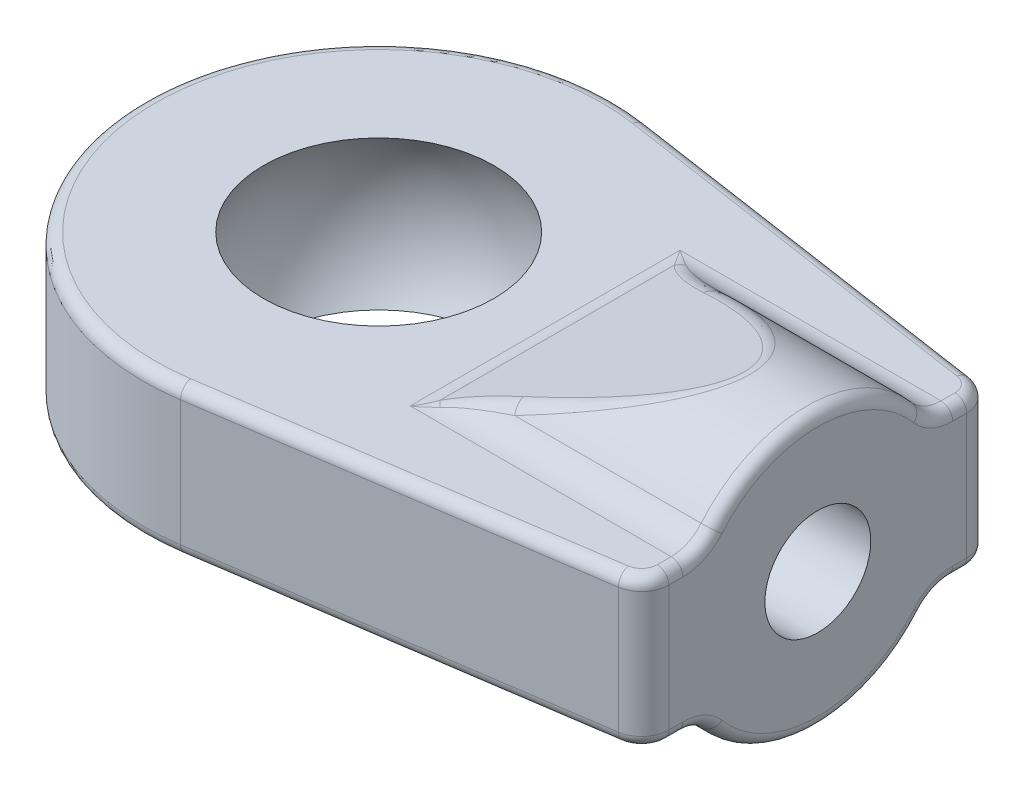
SolidWorks part; units mm, degrees
ref_plane "Front Plane" through (0, 0, 0) normal (0, 0, 1) x (1, 0, 0)
ref_plane "Top Plane" through (0, 0, 0) normal (0, 1, 0) x (1, 0, 0)
ref_plane "Right Plane" through (0, 0, 0) normal (1, 0, 0) x (0, 0, -1)
sketch "Sketch1" plane through (0, 0, 0) normal (0, 1, 0) x (1, 0, 0)
  line L0 (11.2, -4.4) -> (11.2, 4.4)
  line L1 (0, 0) -> (21.1903, 0) construction
  line L2 (11.2, 4.4) -> (0.8828, 5.9347)
  line L3 (11.2, -4.4) -> (0.8828, -5.9347)
  arc A0 (0.8828, 5.9347) -> (0.8828, -5.9347) centre (0, 0) ccw
  point P7 (11.2, 0)
  dimension "D1" = 6
  dimension "D2" = 11.2
  dimension "D3" = 8.8
extrude "Boss-Extrude1" add sketch "Sketch1" along normal blind 1.9 and the other way blind 1.9
sketch "Sketch2" plane through (0, 0, 0) normal (0, 1, 0) x (1, 0, 0)
  line L0 (11.2, 0) -> (11.2, 3.5)
  line L1 (11.2, -4.4) -> (11.2, 4.4) construction
  line L2 (11.2, 3.5) -> (4.4, 3.5)
  line L3 (4.4, 3.5) -> (4.4, 0)
  line L7 (4.4, 0) -> (11.2, 0)
  dimension "D1" = 3.5
  dimension "D2" = 6.8
revolve "Revolve2" add sketch "Sketch2" angle 360 about L1
sketch "Sketch4" plane through (0, 0, 0) normal (0, 1, 0) x (1, 0, 0)
  line L0 (3.5, 0) -> (-3.5, 0)
  arc A0 (3.5, 0) -> (-3.5, 0) centre (0, 0) ccw
  dimension "D1" = 3.5
revolve "Cut-Revolve1" cut sketch "Sketch4" angle 360 about L1
sketch "Sketch5" plane through (0, 0, 0) normal (0, 0, 1) x (1, 0, 0)
  line L0 (4.4, 1.9) -> (9.4, 3.5)
  line L1 (11.2, 3.5) -> (4.4, 3.5) construction
  line L2 (9.4, 3.5) -> (4.4, 3.5)
  line L3 (4.4, 3.5) -> (4.4, 1.9) construction
  line L4 (4.4, 3.5) -> (4.4, 1.9)
  line L5 (-7.2514, 0) -> (14.0046, 0) construction
  line L6 (0, 0) -> (21.1903, 0) construction
  line L7 (4.4, -3.5) -> (4.4, -1.9)
  line L8 (9.4, -3.5) -> (4.4, -3.5)
  line L9 (4.4, -1.9) -> (9.4, -3.5)
  dimension "D1" = 1.8
extrude "Cut-Extrude1" cut sketch "Sketch5" against normal up to next and the other way up to next
fillet "Fillet1" radius 1 6 edges at (4.4, 1.9, 0) (4.4, -1.9, 0) (7.8, -1.9, 2.9394) (7.8, -1.9, -2.9394) (7.8, 1.9, -2.9394) (7.8, 1.9, 2.9394)
fillet "Fillet2" radius 0.5 10 edges at (4.3981, -1.912, 3.2867) (4.9285, -2.0691, 2.8845) (4.3981, -1.912, -3.2867) (4.9285, -2.0691, -2.8845) (4.3981, 1.912, -3.2867) (4.9285, 2.0691, -2.8845) (4.3981, 1.912, 3.2867) (4.9285, 2.0691, 2.8845) (9.4, -3.5, 0) (9.4, 3.5, 0)
sketch "Sketch6" plane through (11.2, 0, 0) normal (1, 0, 0) x (0, 0, -1)
  circle A0 centre (0, 0) radius 1.35
  dimension "D1" = 2.7
extrude "Cut-Extrude2" cut sketch "Sketch6" against normal blind 7
fillet "Fillet3" radius 0.7 2 edges at (11.2, 0, 4.4) (11.2, 0, -4.4)
fillet "Fillet4" radius 0.3 20 edges at (11.0301, -1.9, -4.2535) (11.2, -1.9, -3.6187) (11.2, -1.9932, -3.0193) (11.2, -3.5, 0) (11.2, -1.9932, 3.0193) (11.2, -1.9, 3.6187) (11.0301, -1.9, 4.2535) (5.7429, -1.9, 5.2118) (-6, -1.9, 0) (11.0301, 1.9, -4.2535) (11.2, 1.9, -3.6187) (11.2, 1.9932, -3.0193) (11.2, 3.5, 0) (11.2, 1.9932, 3.0193) (11.2, 1.9, 3.6187) (11.0301, 1.9, 4.2535) (5.7429, 1.9, 5.2118) (-6, 1.9, 0) (5.7429, -1.9, -5.2118) (5.7429, 1.9, -5.2118)
